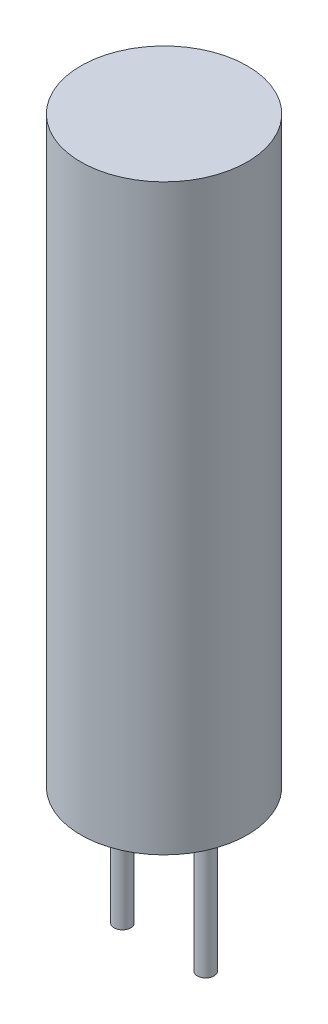
SolidWorks part; units mm, degrees
ref_plane "Front Plane" through (0, 0, 0) normal (0, 0, 1) x (1, 0, 0)
ref_plane "Top Plane" through (0, 0, 0) normal (0, 1, 0) x (1, 0, 0)
ref_plane "Right Plane" through (0, 0, 0) normal (1, 0, 0) x (0, 0, -1)
sketch "SK Electrode pins" plane through (0, 0, 0) normal (0, 1, 0) x (1, 0, 0)
  circle A0 centre (-3, 0) radius 0.6
  circle A1 centre (3, 0) radius 0.6
extrude "Electrode pins" add sketch "SK Electrode pins" along normal blind 10 separate body
sketch "SK Probe body" plane through (0, 0, 0) normal (0, 1, 0) x (1, 0, 0)
  circle A0 centre (0, 0) radius 6
extrude "Probe body" add sketch "SK Probe body" along normal blind 42 from offset 10 separate body
sketch "SK Strain relief" plane through (0, 0, 0) normal (0, 1, 0) x (1, 0, 0)
  circle A0 centre (0, 0) radius 3
extrude "Strain relief" [suppressed] add sketch "SK Strain relief" along normal blind 8 from offset 52 separate body
sketch "SK Cable" plane through (0, 0, 0) normal (0, 1, 0) x (1, 0, 0)
  circle A0 centre (0, 0) radius 1.75
extrude "Cable" [suppressed] add sketch "SK Cable" along normal blind 40 from offset 60 separate body
